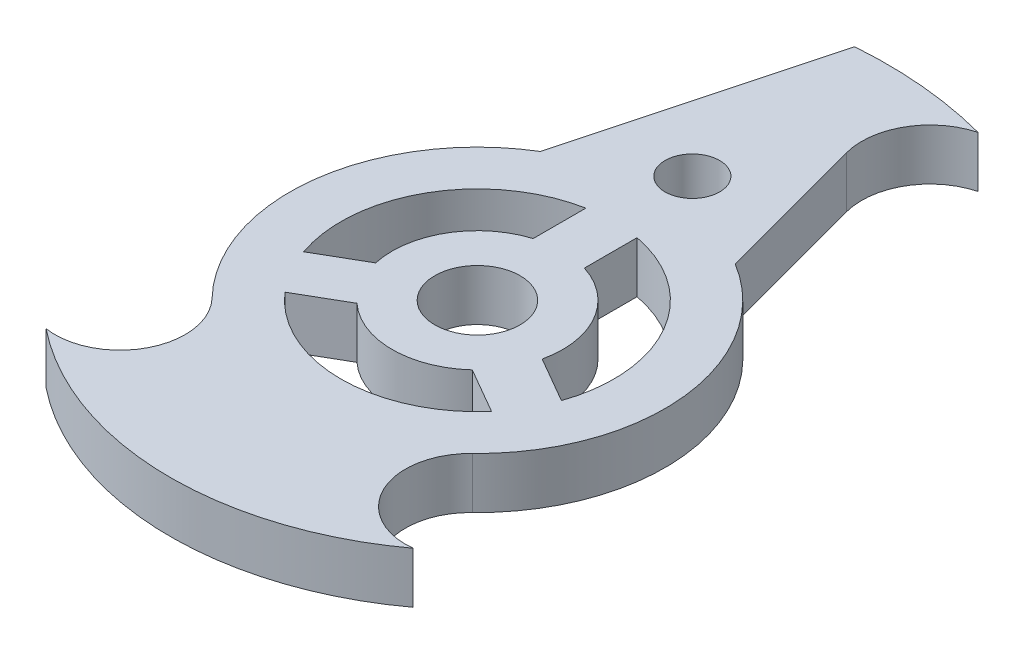
SolidWorks part; units mm, degrees
material "AISI Type A2 Tool Steel"
ref_plane "Front Plane" through (0, 0, 0) normal (0, 0, 1) x (1, 0, 0)
ref_plane "Top Plane" through (0, 0, 0) normal (0, 1, 0) x (1, 0, 0)
ref_plane "Right Plane" through (0, 0, 0) normal (1, 0, 0) x (0, 0, -1)
other "Center of Mass"
other "Bounding Box"
ref_plane "Default Plane" through (-8.9266, -12.7485, 0) normal (-0.1736, 0.9848, 0) x (0.9848, 0.1736, 0)
sketch "Sketch1" plane through (0, 0, 0) normal (0, 1, 0) x (1, 0, 0)
  circle A0 centre (0, 0) radius 7.9375
  circle A1 centre (0, 0) radius 34.925
  circle A2 centre (0, 0) radius 76.2 construction
  dimension "D1" = 15.875
  dimension "D2" = 152.4
  dimension "D3" = 69.85
extrude "Boss-Extrude1" add sketch "Sketch1" along normal mid plane 9.525
sketch "Sketch2" plane through (0, 4.7625, 0) normal (0, 1, 0) x (1, 0, 0)
  line L0 (-18.1431, 29.8427) -> (-5.7805, 75.9804)
  line L1 (18.1431, 29.8427) -> (10.5677, 58.1143)
  line L2 (-5.7805, 75.9804) -> (19.5132, 73.6592) construction
  line L3 (0, 0) -> (0, 76.2) construction
  line L4 (0, 0) -> (19.5132, 73.6592) construction
  line L5 (19.5132, 73.6592) -> (-54.0341, 53.7285) construction
  line L6 (-18.1431, 29.8427) -> (0, 29.8427) construction
  line L7 (0, 29.8427) -> (18.1431, 29.8427) construction
  line L8 (-5.7805, 75.9804) -> (0, 97.5536) construction
  line L9 (0, 97.5536) -> (10.5677, 58.1143) construction
  circle A0 centre (0, 0) radius 34.925 construction
  circle A1 centre (0, 0) radius 76.2 construction
  arc A2 (-5.7805, 75.9804) -> (19.5132, 73.6592) centre (0, 0) cw
  arc A3 (10.5677, 58.1143) -> (19.5132, 73.6592) centre (22.835, 61.4013) cw
  arc A4 (18.1431, 29.8427) -> (-18.1431, 29.8427) centre (0, 0) ccw
  circle A5 centre (0, 0) radius 34.925 construction
  dimension "D1" = 60
  dimension "D3" = 12.7
  dimension "D2" = 25.4
  dimension "D4" = 30
extrude "Boss-Extrude2" add sketch "Sketch2" against normal up to surface (9.525 mm away) up to face at (0, -4.7625, 34.925)
sketch "Sketch3" plane through (0, 4.7625, 0) normal (0, 1, 0) x (1, 0, 0)
  line L0 (-35.5767, -44.7261) -> (0, 0) construction
  line L1 (0, 0) -> (33.9941, -45.9404) construction
  line L2 (0, 0) -> (0, -76.2) construction
  line L3 (0, 0) -> (-1.3299, -76.1884) construction
  line L4 (-35.5767, -44.7261) -> (49.9863, -57.5135) construction
  arc A0 (-35.5767, -44.7261) -> (33.9941, -45.9404) centre (0, 0) ccw
  arc A1 (-35.5767, -44.7261) -> (-25.0811, -24.3042) centre (-33.7852, -32.7388) ccw
  circle A2 centre (0, 0) radius 34.925 construction
  arc A3 (33.9941, -45.9404) -> (24.2176, -25.1648) centre (32.6221, -33.8979) cw
  arc A4 (-25.0811, -24.3042) -> (24.2176, -25.1648) centre (0, 0) ccw
  circle A5 centre (0, 0) radius 76.2 construction
  point P6 (-0.9974, -57.1413)
  dimension "D1" = 57.15
  dimension "D2" = 75
  dimension "D3" = 1
  dimension "D4" = 60
extrude "Boss-Extrude3" add sketch "Sketch3" against normal up to surface (9.525 mm away) up to face at (4.237, -4.7625, -41.1164)
sketch "Sketch4" plane through (0, 4.7625, 0) normal (0, 1, 0) x (1, 0, 0)
  line L0 (15.4962, -3.4474) -> (23.9882, -8.3503)
  line L1 (4.7625, 15.1438) -> (4.7625, 24.9495)
  line L2 (0, 0) -> (30.2459, -17.4625) construction
  line L3 (0, 0) -> (0, 34.925) construction
  line L4 (4.7625, 24.9495) -> (0, 24.9495) construction
  line L5 (23.9882, -8.3503) -> (21.6069, -12.4748) construction
  arc A0 (4.7625, 15.1438) -> (15.4962, -3.4474) centre (0, 0) cw
  arc A1 (4.7625, 24.9495) -> (23.9882, -8.3503) centre (0, 0) cw
  circle A2 centre (0, 0) radius 34.925 construction
  dimension "D2" = 9.525
  dimension "D3" = 15.875
  dimension "D1" = 4.7625
  dimension "D4" = 120
extrude "Cut-Extrude1" cut sketch "Sketch4" against normal through all
pattern_circular "CirPattern1" count 3 over 360 about axis through (0, 4.7625, 0) along (0, -1, 0) of "Cut-Extrude1" reverse direction yes
sketch "Sketch5" plane through (0, 4.7625, 0) normal (0, 1, 0) x (1, 0, 0)
  line L0 (0, 0) -> (0, 76.2) construction
  circle A0 centre (0, 40.005) radius 5.08
  arc A1 (18.1431, 29.8427) -> (-18.1431, 29.8427) centre (0, 0) ccw construction
  dimension "D1" = 10.16
extrude "Cut-Extrude2" cut sketch "Sketch5" against normal through all
